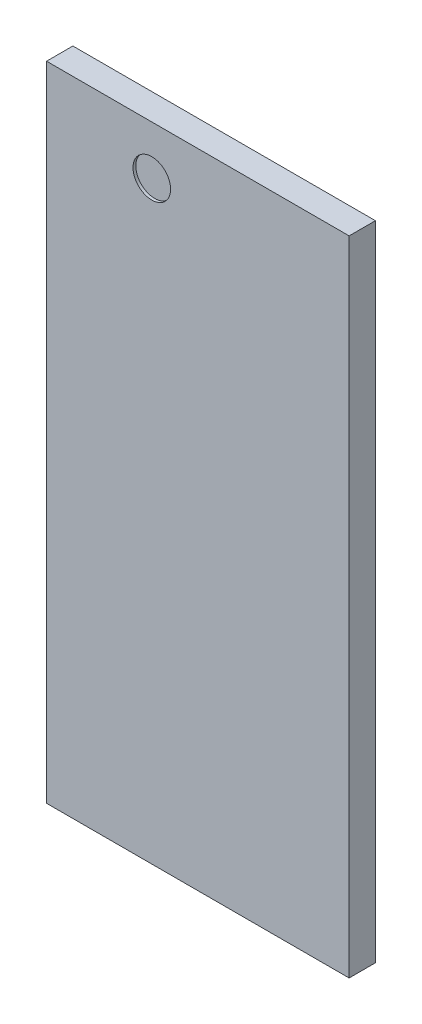
SolidWorks part; units mm, degrees
ref_plane "前视基准面" through (0, 0, 0) normal (0, 0, 1) x (1, 0, 0)
ref_plane "上视基准面" through (0, 0, 0) normal (0, 1, 0) x (1, 0, 0)
ref_plane "右视基准面" through (0, 0, 0) normal (1, 0, 0) x (0, 0, -1)
other "Configuration Table"
sketch "草图1" plane through (0, 0, 0) normal (0, 0, 1) x (1, 0, 0)
  line L1 (-80.5, 171) -> (80.5, 171)
  line L2 (-80.5, 171) -> (-80.5, -171)
  line L3 (-80.5, -171) -> (80.5, -171)
  line L4 (80.5, 171) -> (80.5, -171)
  line L5 (-80.5, 171) -> (80.5, -171) construction
  line L6 (-80.5, -171) -> (80.5, 171) construction
  circle A0 centre (-24.5, 145) radius 10
  point P0 (0, 0)
  dimension "D5" = 20
  dimension "D1" = 161
  dimension "D2" = 342
  dimension "D3" = 56
  dimension "D4" = 26
extrude "凸台-拉伸1" add sketch "草图1" against normal blind 14 contours L1 L4 L3 L2
extrude "切除-拉伸1" cut sketch "草图1<3>" against normal blind 1.5 contours A0
sketch "草图1<3>" plane through (0, 0, 0) normal (0, 0, 1) x (1, 0, 0) same geometry as "草图1"
